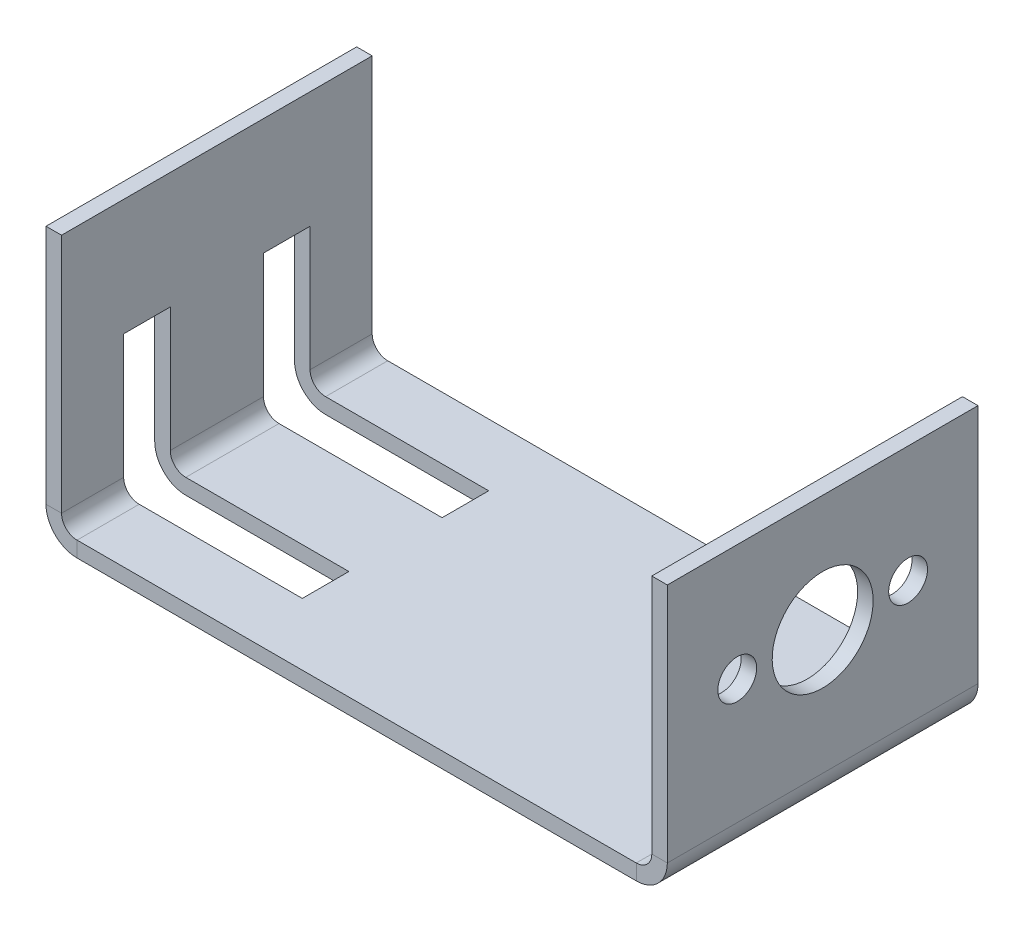
SolidWorks part; units mm, degrees
note: The reader was unsure of these and kept them because the rebuilt part matched: flange length of "Edge-Flange1".
ref_plane "Front Plane" through (0, 0, 0) normal (0, 0, 1) x (1, 0, 0)
ref_plane "Top Plane" through (0, 0, 0) normal (0, 1, 0) x (1, 0, 0)
ref_plane "Right Plane" through (0, 0, 0) normal (1, 0, 0) x (0, 0, -1)
sketch "Sketch1" plane through (0, 0, 0) normal (0, 1, 0) x (1, 0, 0)
  line L1 (40, 20) -> (-40, 20)
  line L2 (40, 20) -> (40, -20)
  line L3 (40, -20) -> (-40, -20)
  line L4 (-40, 20) -> (-40, -20)
  line L5 (40, 20) -> (-40, -20) construction
  line L6 (40, -20) -> (-40, 20) construction
  point P0 (0, 0)
  dimension "D1" = 40
  dimension "D2" = 80
base flange "Base-Flange1" sketch "Sketch1" thickness 2 reverse thickness direction no parameters "D1"=0.7366
edge flange "Edge-Flange1" sketch "Sketch10" flange profiles "Sketch10", "Sketch11" flange angle 90 flange length 35 flange position material inside bend radius 2 thickness 2 relief rectangular parameters "D6"=10, "D8"=1
sketch "Sketch10" plane through (-40, 0, 0) normal (-1, 0, 0) x (0, 0, 1)
  line L2 (-20, 0) -> (-20, 33)
  line L3 (-20, 33) -> (20, 33)
  line L4 (20, 33) -> (20, 0)
  line L7 (-20, 0) -> (20, 0) construction
  line L8 (-20, 0) -> (20, 0)
sketch "Sketch11" plane through (40, 0, 0) normal (1, 0, 0) x (0, 0, -1)
  line L0 (-20, 0) -> (20, 0) construction
  line L1 (-20, 0) -> (20, 0)
  line L2 (-20, 0) -> (-20, 33)
  line L3 (-20, 33) -> (20, 33)
  line L4 (20, 33) -> (20, 0)
bend "EdgeBend1" bend radius 2 bend angle 90 parameters "D5"=1
bend "EdgeBend2" bend radius 2 bend angle 90 parameters "D5"=2
sketch "Sketch12" plane through (40, 0, 0) normal (1, 0, 0) x (0, 0, -1)
  line L0 (0, 18) -> (0, 0) construction
  line L1 (20, -2) -> (-20, -2) construction
  circle A0 centre (0, 18) radius 6.5
  circle A1 centre (-11, 18) radius 2.5
  circle A2 centre (11, 18) radius 2.5
  point P10 (0, 0)
  point P11 (0, 0)
  dimension "D1" = 5
  dimension "D2" = 13
  dimension "D3" = 22
  dimension "D4" = 20
extrude "Cut-Extrude1" cut sketch "Sketch12" against normal blind 10
sketch "Sketch13" plane through (-40, 0, 0) normal (-1, 0, 0) x (0, 0, 1)
  line L0 (0, 0) -> (0, 14.7347) construction
  line L1 (20, -2) -> (-20, -2) construction
  line L2 (6, -22) -> (12, -22)
  line L3 (6, -22) -> (6, 18)
  line L4 (6, 18) -> (12, 18)
  line L5 (12, -22) -> (12, 18)
  line L6 (6, -22) -> (12, 18) construction
  line L7 (6, 18) -> (12, -22) construction
  line L8 (-6, 18) -> (-12, 18)
  line L9 (-12, -22) -> (-12, 18)
  line L10 (-6, -22) -> (-12, -22)
  line L11 (-6, -22) -> (-6, 18)
  point P3 (9, -2)
  dimension "D1" = 6
  dimension "D2" = 12
  dimension "D3" = 20
extrude "Cut-Extrude2" cut sketch "Sketch13" against normal blind 25
sketch "Bend-Lines1" [suppressed] plane through (0, 0, 0) normal (0, 1, 0) x (1, 0, 0)
sketch "Bounding-Box1" [suppressed] plane through (0, 0, 0) normal (0, 1, 0) x (1, 0, 0)
sheet metal parameters "Sheet-Metal1" thickness 2 parameters "D1"=0.7366
flat pattern "Flat-Pattern1" [suppressed]
sketch "Bend-Lines2" plane through (0, 0, 0) normal (0, 1, 0) x (1, 0, 0)
sketch3d "Bounding-Box2" [suppressed]
  line L0 (-40, 20, 0) -> (40, 20, 0) construction
  line L1 (-40, -20, 0) -> (40, -20, 0) construction
  line L2 (-40, 20, 0) -> (-40, -20, 0) construction
  line L3 (40, 20, 0) -> (40, -20, 0) construction
sheet metal parameters "Sheet-Metal2" thickness 2 parameters "D1"=0.7366
flat pattern "Flat-Pattern1"
sketch "Bend-Lines2" plane through (0, 0, 0) normal (0, 1, 0) x (1, 0, 0)
  line L0 (38.6273, -20) -> (38.6273, 20) construction
  line L1 (-38.6273, 20) -> (-38.6273, -20) construction
  line L2 (38.6273, -20) -> (38.6273, 20) construction
  line L3 (-38.6273, 20) -> (-38.6273, -20) construction
sketch3d "Bounding-Box2" [suppressed]
  line L0 (72.2546, 20, 0) -> (-72.2546, 20, 0) construction
  line L1 (72.2546, -20, 0) -> (-72.2546, -20, 0) construction
  line L2 (72.2546, 20, 0) -> (72.2546, -20, 0) construction
  line L3 (-72.2546, 20, 0) -> (-72.2546, -20, 0) construction
bend of the flat pattern "Flatten-<EdgeBend1>1"
bend of the flat pattern "Flatten-<EdgeBend2>1"
sheet metal parameters "Sheet-Metal3" thickness 2 parameters "D1"=0.7366
flat pattern "Flat-Pattern1"
sketch "Bend-Lines2" plane through (0, 0, 0) normal (0, 1, 0) x (1, 0, 0)
  line L0 (38.6273, -20) -> (38.6273, 20) construction
  line L1 (-38.6273, 20) -> (-38.6273, -20) construction
  line L2 (38.6273, -20) -> (38.6273, 20) construction
  line L3 (-38.6273, 20) -> (-38.6273, -20) construction
sketch3d "Bounding-Box2" [suppressed]
  line L0 (72.2546, 20, 0) -> (-72.2546, 20, 0) construction
  line L1 (72.2546, -20, 0) -> (-72.2546, -20, 0) construction
  line L2 (72.2546, 20, 0) -> (72.2546, -20, 0) construction
  line L3 (-72.2546, 20, 0) -> (-72.2546, -20, 0) construction
bend of the flat pattern "Flatten-<EdgeBend1>1"
bend of the flat pattern "Flatten-<EdgeBend2>1"
sheet metal parameters "Sheet-Metal4" thickness 2 parameters "D1"=0.7366
flat pattern "Flat-Pattern1"
sketch "Bend-Lines2" plane through (0, 0, 0) normal (0, 1, 0) x (1, 0, 0)
  line L0 (38.3562, -20) -> (38.3562, 20) construction
  line L1 (-38.3562, -12) -> (-38.3562, -20) construction
  line L2 (38.3562, -20) -> (38.3562, 20) construction
  line L3 (-38.3562, -12) -> (-38.3562, -20) construction
  line L4 (-38.3562, 20) -> (-38.3562, 12) construction
  line L5 (-38.3562, 6) -> (-38.3562, -6) construction
sketch3d "Bounding-Box2" [suppressed]
  line L0 (71.7124, 20, 0) -> (-71.7124, 20, 0) construction
  line L1 (71.7124, -20, 0) -> (-71.7124, -20, 0) construction
  line L2 (71.7124, 20, 0) -> (71.7124, -20, 0) construction
  line L3 (-71.7124, 20, 0) -> (-71.7124, -20, 0) construction
bend of the flat pattern "Flatten-<EdgeBend1>1"
bend of the flat pattern "Flatten-<EdgeBend2>1"
